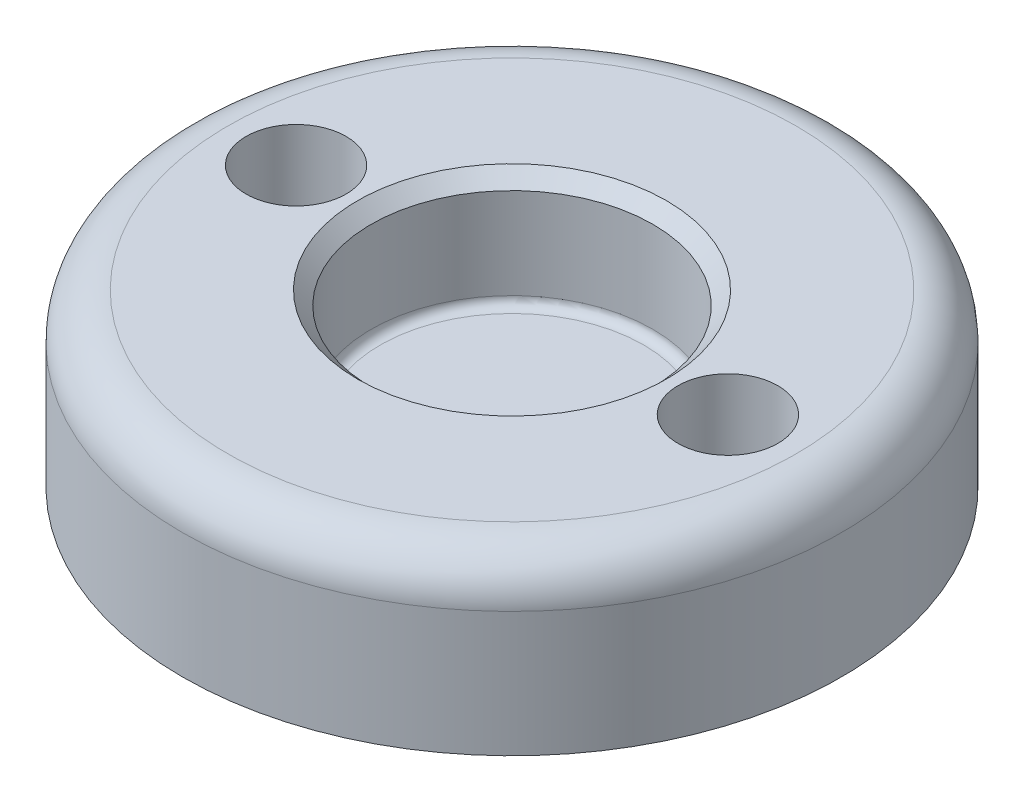
SolidWorks part; units mm, degrees
material "Brass"
ref_plane "Front Plane" through (0, 0, 0) normal (0, 0, 1) x (1, 0, 0)
ref_plane "Top Plane" through (0, 0, 0) normal (0, 1, 0) x (1, 0, 0)
ref_plane "Right Plane" through (0, 0, 0) normal (1, 0, 0) x (0, 0, -1)
sketch "Sketch1" plane through (0, 0, 0) normal (0, 0, 1) x (1, 0, 0)
  line L0 (0, 0) -> (0, 7.0462) construction
  line L1 (0, 0) -> (-7.25, 0)
  line L2 (-7.25, 0) -> (-7.25, 3.75)
  line L3 (-7.25, 3.75) -> (-3.1, 3.75)
  line L4 (-3.1, 3.75) -> (-3.1, 1.25)
  line L5 (-3.1, 1.25) -> (0, 1.25)
  line L6 (0, 0) -> (0, 1.25)
  dimension "D1" = 3.1
  dimension "D2" = 4.15
  dimension "D3" = 1.25
  dimension "D4" = 2.5
  dimension "D5" = 7.25
revolve "Revolve1" add sketch "Sketch1" angle 360 about L0
chamfer "Chamfer2" distance 0.3 angle 45 1 edges at (0, 3.75, -3.1)
sketch "Sketch2" plane through (0, 3.75, 0) normal (0, 1, 0) x (1, 0, 0)
  line L0 (-6.8053, -2.5) -> (-12.25, -2.5)
  line L1 (-12.25, -2.5) -> (-12.25, 2.5)
  line L2 (-12.25, 2.5) -> (-6.8053, 2.5)
  line L3 (-12.25, 0) -> (-7.25, 0) construction
  circle A0 centre (0, 0) radius 7.25 construction
  arc A1 (-6.8053, 2.5) -> (-6.8053, -2.5) centre (0, 0) ccw
  point P2 (-12.25, 0)
  dimension "D1" = 5
extrude "Boss-Extrude1" [suppressed] add sketch "Sketch2" against normal up to surface (3 mm away) up to face at (0, 0, -7.25)
hole_wizard "CSK for M2 Flat Head Machine Screw1" positions "Sketch3" profile "Sketch4" countersink size "M2" standard "ANSI Metric"
sketch "Sketch3" plane through (0, 0, 0) normal (0, -1, 0) x (-1, 0, 0)
  point P0 (4.75, 0)
  dimension "D1" = 4.75
sketch "Sketch4" plane through (-4.75, 0, 0) normal (1, 0, 0) x (0, 0, -1)
  line L0 (0, 0) -> (0, 5.6609)
  line L1 (0, 5.6609) -> (1.1, 5)
  line L2 (1.1, 5) -> (1.1, 1.1)
  line L3 (1.1, 1.1) -> (2.2, 0)
  line L5 (2.2, 0) -> (0, 0)
  line L6 (-1.1, 1.1) -> (-2.2, 0) construction
  line L10 (0, 5.6609) -> (-1.1, 5) construction
  line L11 (0, -6.35) -> (0, 107.95) construction
  dimension "Hole Dia." = 2.2
  dimension "Hole Depth" = 5
  dimension "Near C'Sink Dia." = 4.4
  dimension "Near C'Sink Angle" = 90
  dimension "Drill Angle" = 118
sketch "Sketch5" [suppressed] plane through (0, 0, 0) normal (0, -1, 0) x (1, 0, 0)
  line L1 (-6.8053, 2.5) -> (-12.25, 2.5) construction
  line L2 (-6.8053, 2.5) -> (-12.25, 2.5) construction
  line L3 (-12.25, -2.5) -> (-6.8053, -2.5) construction
  line L4 (-4.75, -2.5) -> (-12.25, -2.5)
  line L5 (-12.25, -2.5) -> (-12.25, 2.5)
  line L9 (-12.25, 2.5) -> (-4.75, 2.5)
  arc A0 (-4.75, -2.5) -> (-4.75, 2.5) centre (-4.75, 0) cw
extrude "Cut-Extrude1" [suppressed] cut sketch "Sketch5" against normal through all both and the other way through all
pattern_circular "CirPattern1" count 2 over 360 about axis through (0, 0, 0) along (0, -1, 0) of "CSK for M2 Flat Head Machine Screw1", "Boss-Extrude1", "Cut-Extrude1" reverse direction yes
fillet "Fillet1" [suppressed] radius 10
fillet "Fillet2" radius 0.2 1 edges at (0, 1.25, -3.1)
fillet "Fillet3" radius 1 1 edges at (0, 3.75, -7.25)
